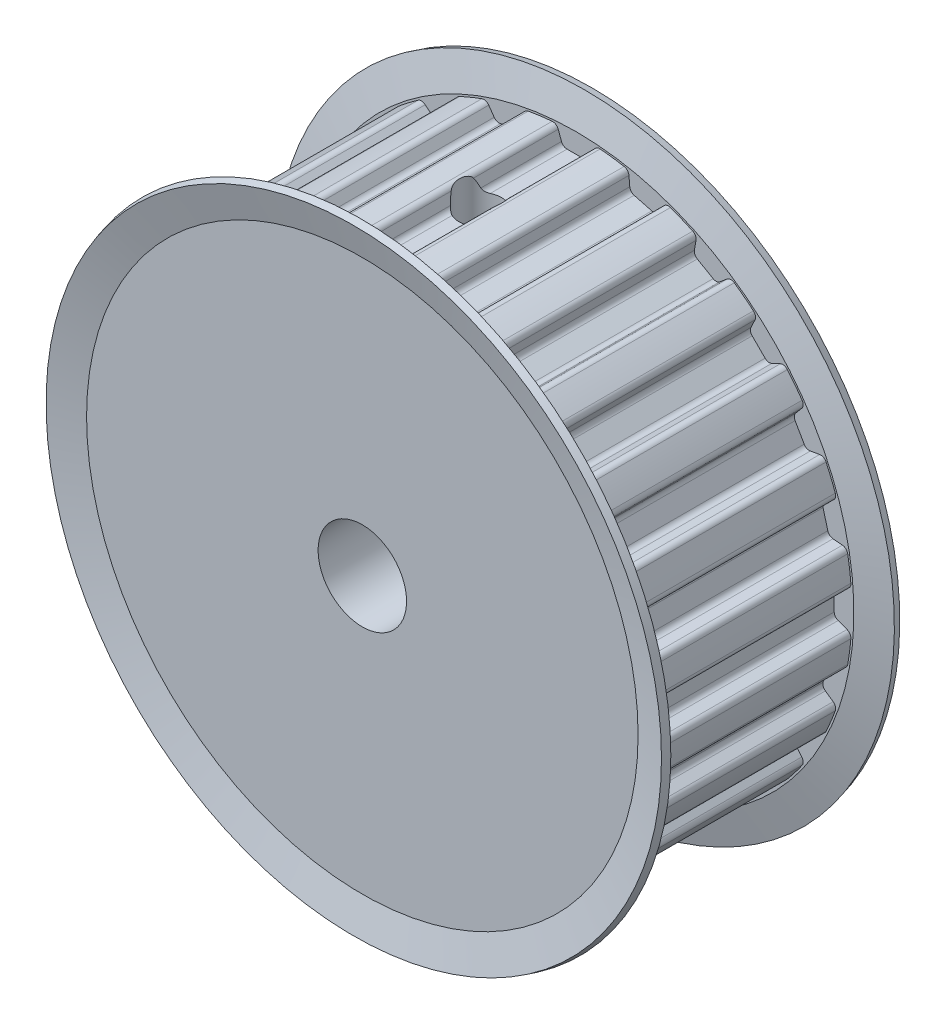
SolidWorks part; units mm, degrees
material "Д16Т ГОСТ 4784-74"
ref_plane "Front" through (0, 0, 0) normal (0, 0, 1) x (1, 0, 0)
ref_plane "Top" through (0, 0, 0) normal (0, 1, 0) x (1, 0, 0)
ref_plane "Right" through (0, 0, 0) normal (1, 0, 0) x (0, 0, -1)
sketch "support-front-body" plane through (0, 0, 0) normal (0, 0, 1) x (1, 0, 0)
  line L0 (0, 0) -> (0, 18.7) construction
  line L1 (0, 0) -> (0, -18.7) construction
  line L2 (0, 0) -> (18.7, 0) construction
  line L3 (0, 0) -> (-18.7, 0) construction
  circle A0 centre (0, 0) radius 18.7
  dimension "diam-outer" = 37.4
sketch "support-right-body" plane through (0, 0, 0) normal (1, 0, 0) x (0, 0, -1)
  line L0 (0, 0) -> (15, 0) construction
  line L1 (0, 18.7) -> (15, 18.7)
  line L2 (0, 18.7) -> (0, -18.7)
  line L3 (0, -18.7) -> (15, -18.7)
  line L4 (15, 18.7) -> (15, -18.7)
  dimension "width" = 15
sketch "support-right-hub" plane through (0, 0, 0) normal (1, 0, 0) x (0, 0, -1)
  line L0 (21, 0) -> (15, 0) construction
  line L1 (15, 13) -> (21, 13)
  line L2 (15, 13) -> (15, -13)
  line L3 (15, -13) -> (21, -13)
  line L4 (21, 13) -> (21, -13)
  line L5 (15, 18.7) -> (15, -18.7) construction
  line L6 (0, 0) -> (15, 0) construction
  line L8 (0, 18.7) -> (0, -18.7) construction
  dimension "diam-hub" = 26
  dimension "dist-hub" = 21
sketch "support-right-bore" plane through (0, 0, 0) normal (1, 0, 0) x (0, 0, -1)
  line L0 (0, 18.7) -> (0, -18.7) construction
  line L1 (0, 3) -> (21, 3)
  line L2 (0, 3) -> (0, -3)
  line L3 (0, -3) -> (21, -3)
  line L4 (21, 13) -> (21, -13) construction
  line L5 (21, 0) -> (0, 0) construction
  line L6 (0, 0) -> (15, 0) construction
  line L7 (21, 3) -> (21, -3)
  line L8 (21, -3) -> (21, 3) construction
  dimension "diam-bore" = 6
sketch "support-stop-screw-hole" plane through (0, 0, 0) normal (1, 0, 0) x (0, 0, -1)
  line L1 (6.5667, 50) -> (9.4333, 50)
  line L2 (6.5667, 50) -> (6.5667, -1)
  line L3 (8, -1) -> (9.4333, -1)
  line L4 (9.4333, 50) -> (9.4333, -1)
  line L5 (8, -1) -> (8, 50) construction
  line L6 (8, -1) -> (6.5667, -1)
  line L7 (0, 0) -> (8, 0) construction
  line L8 (0, 18.7) -> (0, -18.7) construction
  dimension "diam-stop-screw-hole" = 2.8665
  dimension "dist-stop-screw-hole" = 8
  dimension "depth-stop-screw-hole" = 51
  dimension "angle-stop-screw-hole" = 180
  dimension "height-stop-screw-hole" = 50
sketch "support-front-keygroove" plane through (0, 0, 0) normal (0, 0, 1) x (1, 0, 0)
  line L0 (0, 0) -> (0, -3) construction
  line L1 (-1, 5) -> (1, 5)
  line L2 (-1, 5) -> (-1, 2.8)
  line L3 (-1, 2.8) -> (1, 2.8)
  line L4 (1, 5) -> (1, 2.8)
  line L5 (0, 0) -> (0, 3) construction
  circle A0 centre (0, 0) radius 3 construction
  dimension "width-keygroove" = 2
  dimension "dist-keygroove" = 8
  dimension "height-keygroove" = 2.2
sketch "support-front-tooth" plane through (0, 0, 0) normal (0, 0, 1) x (1, 0, 0)
  line L0 (0, 0) -> (0, 19.8291) construction
  line L1 (-1.2157, 18.3675) -> (-0.9958, 17.7632)
  line L2 (-1.6264, 19.8291) -> (1.6264, 19.8291)
  line L3 (1.6264, 19.8291) -> (1.6264, 18.6291)
  line L4 (-1.6264, 19.8291) -> (-1.6264, 18.6291)
  line L5 (-2.5, 19.8291) -> (2.5, 19.8291) construction
  line L6 (1.6264, 18.6291) -> (2.5, 19.8291) construction
  line L7 (0, 18.7) -> (0, 17.5) construction
  line L8 (0, 18.7) -> (1.6264, 18.7) construction
  line L10 (-0.6199, 17.5) -> (0.6199, 17.5)
  line L11 (1.2157, 18.3675) -> (0.9958, 17.7632)
  line L12 (-0.9958, 17.7632) -> (-0.9, 17.5) construction
  line L13 (-0.9, 17.5) -> (-0.6199, 17.5) construction
  line L14 (0.9958, 17.7632) -> (0.9, 17.5) construction
  line L15 (0.9, 17.5) -> (0.6199, 17.5) construction
  circle A0 centre (0, 0) radius 18.7 construction
  arc A1 (-0.9958, 17.7632) -> (-0.6199, 17.5) centre (-0.6199, 17.9) ccw
  arc A3 (1.6264, 18.6291) -> (1.2157, 18.3675) centre (1.5916, 18.2307) ccw
  circle A4 centre (0, 0) radius 18.7 construction
  arc A5 (-1.6264, 18.6291) -> (-1.2157, 18.3675) centre (-1.5916, 18.2307) cw
  arc A6 (0.9958, 17.7632) -> (0.6199, 17.5) centre (0.6199, 17.9) cw
  point P26 (0, 17.5)
  dimension "rad-top" = 0.4
  dimension "rad-bottom" = 0.4
  dimension "height-tooth" = 1.2
  dimension "pitch" = 5
  dimension "angle" = 40
  dimension "width-tooth-bottom" = 1.8
sketch "support-right-flange" plane through (0, 0, 0) normal (1, 0, 0) x (0, 0, -1)
  line L0 (0, 16.625) -> (0, 18.7)
  line L1 (15, 18.7) -> (15, -18.7) construction
  line L2 (0, 18.7) -> (0.5, 18.7) construction
  line L3 (0.5, 18.834) -> (-0.0804, 21)
  line L4 (-0.5804, 20.866) -> (-0.0804, 21)
  line L5 (0.5, 18.834) -> (0.5, 16.625)
  line L6 (0.5, 16.625) -> (0, 16.625)
  line L7 (7.5, 18.7) -> (7.5, 0) construction
  line L8 (0, 18.7) -> (15, 18.7) construction
  line L9 (0, 18.7) -> (-0.5804, 20.866)
  line L10 (14.5, 16.625) -> (15, 16.625)
  line L11 (14.5, 18.834) -> (14.5, 16.625)
  line L12 (15.5804, 20.866) -> (15.0804, 21)
  line L13 (14.5, 18.834) -> (15.0804, 21)
  line L14 (15, 18.7) -> (15.5804, 20.866)
  line L15 (15, 16.625) -> (15, 18.7)
  line L16 (15, 0) -> (0, 0) construction
  line L17 (15, -16.625) -> (15, -18.7)
  line L18 (15, -18.7) -> (15.5804, -20.866)
  line L19 (14.5, -18.834) -> (15.0804, -21)
  line L20 (15.5804, -20.866) -> (15.0804, -21)
  line L21 (14.5, -18.834) -> (14.5, -16.625)
  line L22 (14.5, -16.625) -> (15, -16.625)
  line L23 (0.5, -16.625) -> (0, -16.625)
  line L24 (0.5, -18.834) -> (0.5, -16.625)
  line L25 (-0.5804, -20.866) -> (-0.0804, -21)
  line L26 (0.5, -18.834) -> (-0.0804, -21)
  line L27 (0, -18.7) -> (-0.5804, -20.866)
  line L28 (0, -16.625) -> (0, -18.7)
  line L29 (0, 0) -> (15, 0) construction
  line L30 (0, 18.7) -> (0.5, 18.834) construction
  line L31 (0.25, 16.625) -> (0.25, 17.6625) construction
  line L32 (0.25, 17.6625) -> (0.25, 18.7) construction
  line L33 (-0.3304, 20.933) -> (0.25, 18.767) construction
  line L34 (0, 18.7) -> (15, 18.7) construction
  line L35 (0, 18.7) -> (0, -18.7) construction
  dimension "angle-flange" = 15
  dimension "thickness-flange" = 0.5
  dimension "diam-flange-inner" = 33.25
  dimension "diam-flange-outer" = 42
  dimension "diam-flange-angle" = 37.4
ref_axis "ref-axis-center" through (0, 0, -15) along (0, 0, 1)
ref_plane "ref-plane-front" through (0, 0, 0) normal (0, 0, 1) x (1, 0, 0)
ref_plane "ref-plane-back" through (0, 0, -15) normal (0, 0, 1) x (1, 0, 0)
ref_plane "ref-plane-hub-front" through (0, 0, -15) normal (0, 0, 1) x (1, 0, 0)
ref_plane "ref-plane-hub-back" through (0, 0, -21) normal (0, 0, 1) x (1, 0, 0)
ref_plane "ref-plane-bore-front" through (0, 0, 0) normal (0, 0, 1) x (1, 0, 0)
ref_plane "ref-plane-bore-back" through (0, 0, -21) normal (0, 0, 1) x (1, 0, 0)
ref_plane "ref-plane-stop-screw-hole-top" through (0, 50, 0) normal (0, 1, 0) x (-1, 0, 0)
ref_axis "ref-axis-stop-screw-hole" through (0, 50, -8) along (0, -1, 0)
sketch "Sketch5" plane through (0, 0, 0) normal (1, 0, 0) x (0, 0, -1)
  line L0 (15, 18.7) -> (15, -18.7) construction
  line L1 (0, 18.7) -> (15, 18.7) construction
  line L2 (0, 18.7) -> (0, -18.7) construction
  line L3 (0, 0) -> (15, 0) construction
  line L4 (15, 18.7) -> (15, 0)
  line L5 (0, 18.7) -> (15, 18.7)
  line L6 (0, 18.7) -> (0, 0)
  line L7 (0, 0) -> (15, 0) construction
  line L8 (0, 0) -> (15, 0)
revolve "body" add sketch "Sketch5" angle 360 about L7
sketch "Sketch16" plane through (0, 0, 0) normal (1, 0, 0) x (0, 0, -1)
  line L0 (21, 13) -> (21, -13) construction
  line L1 (15, 13) -> (21, 13) construction
  line L2 (21, 0) -> (15, 0) construction
  line L3 (15, 13) -> (15, -13) construction
  line L4 (21, 13) -> (21, 0)
  line L5 (15, 13) -> (21, 13)
  line L6 (21, 0) -> (15, 0) construction
  line L7 (15, 13) -> (15, 0)
  line L8 (21, 0) -> (15, 0)
revolve "body-hub" add sketch "Sketch16" angle 360 about L6
sketch "Sketch17" plane through (0, 0, 0) normal (1, 0, 0) x (0, 0, -1)
  line L1 (21, 0) -> (0, 0) construction
  line L2 (0, 3) -> (21, 3) construction
  line L3 (0, 3) -> (0, -3) construction
  line L4 (21, 3) -> (21, -3) construction
  line L5 (21, 0) -> (0, 0) construction
  line L6 (0, 3) -> (21, 3)
  line L7 (0, 3) -> (0, 0)
  line L8 (21, 0) -> (0, 0)
  line L9 (21, 3) -> (21, 0)
revolve "body-bore" cut sketch "Sketch17" angle 360 about L5
sketch "Sketch19" plane through (0, 0, 0) normal (1, 0, 0) x (0, 0, -1)
  line L0 (6.5667, 50) -> (9.4333, 50) construction
  line L1 (8, -1) -> (8, 50) construction
  line L2 (9.4333, 50) -> (9.4333, -1) construction
  line L3 (8, -1) -> (9.4333, -1) construction
  line L4 (8, 50) -> (9.4333, 50)
  line L5 (8, -1) -> (8, 50) construction
  line L6 (9.4333, 50) -> (9.4333, -1)
  line L7 (8, -1) -> (9.4333, -1)
  line L8 (8, -1) -> (8, 50)
revolve "body-stop-screw-hole" cut sketch "Sketch19" angle 360 about L5
pattern_circular "pattern-stop-screw-hole" [suppressed] count 2 every 90 about axis through (0, 0, -15) along (0, 0, 1)
sketch "Sketch21" plane through (0, 0, 0) normal (0, 0, 1) x (1, 0, 0)
  line L0 (-1, 5) -> (1, 5) construction
  line L1 (-1, 5) -> (-1, 2.8) construction
  line L2 (-1, 2.8) -> (1, 2.8) construction
  line L3 (1, 5) -> (1, 2.8) construction
  line L4 (-1, 5) -> (1, 5)
  line L5 (-1, 5) -> (-1, 2.8)
  line L6 (-1, 2.8) -> (1, 2.8)
  line L7 (1, 5) -> (1, 2.8)
extrude "cut-keygroove" [suppressed] cut sketch "Sketch21" against normal up to surface (17.5 mm away)
sketch "Sketch23" plane through (0, 0, 0) normal (0, 0, 1) x (1, 0, 0)
  line L6 (1.6264, 19.8291) -> (-1.6264, 19.8291)
  line L7 (1.6264, 18.6291) -> (1.6264, 19.8291)
  line L8 (0.9958, 17.7632) -> (1.2157, 18.3675)
  line L9 (-0.6199, 17.5) -> (0.6199, 17.5)
  line L10 (-1.2157, 18.3675) -> (-0.9958, 17.7632)
  line L11 (-1.6264, 19.8291) -> (-1.6264, 18.6291)
  line L12 (1.6264, 19.8291) -> (-1.6264, 19.8291)
  line L13 (1.6264, 18.6291) -> (1.6264, 19.8291)
  line L14 (0.9958, 17.7632) -> (1.2157, 18.3675)
  line L15 (-0.6199, 17.5) -> (0.6199, 17.5)
  line L16 (-1.2157, 18.3675) -> (-0.9958, 17.7632)
  line L17 (-1.6264, 19.8291) -> (-1.6264, 18.6291)
  arc A4 (1.6264, 18.6291) -> (1.2157, 18.3675) centre (1.5916, 18.2307) ccw
  arc A5 (0.6199, 17.5) -> (0.9958, 17.7632) centre (0.6199, 17.9) ccw
  arc A6 (-0.9958, 17.7632) -> (-0.6199, 17.5) centre (-0.6199, 17.9) ccw
  arc A7 (-1.2157, 18.3675) -> (-1.6264, 18.6291) centre (-1.5916, 18.2307) ccw
  arc A8 (1.6264, 18.6291) -> (1.2157, 18.3675) centre (1.5916, 18.2307) ccw
  arc A9 (0.6199, 17.5) -> (0.9958, 17.7632) centre (0.6199, 17.9) ccw
  arc A10 (-0.9958, 17.7632) -> (-0.6199, 17.5) centre (-0.6199, 17.9) ccw
  arc A11 (-1.2157, 18.3675) -> (-1.6264, 18.6291) centre (-1.5916, 18.2307) ccw
  dimension "D1" = 0
extrude "cut-tooth" cut sketch "Sketch23" against normal up to surface (15 mm away) up to plane "ref-plane-back"
pattern_circular "pattern-tooth" count 24 over 360 about axis through (0, 0, -15) along (0, 0, 1) of "cut-tooth"
sketch "Sketch25" plane through (0, 0, 0) normal (1, 0, 0) x (0, 0, -1)
  line L0 (0, 0) -> (15, 0) construction
  line L1 (0.5, 16.625) -> (0, 16.625) construction
  line L2 (0.5, 18.834) -> (0.5, 16.625) construction
  line L4 (-0.5804, 20.866) -> (-0.0804, 21) construction
  line L5 (0, 18.7) -> (-0.5804, 20.866) construction
  line L6 (0, 16.625) -> (0, 18.7) construction
  line L7 (0, 0) -> (15, 0) construction
  line L8 (0.5, 16.625) -> (0, 16.625)
  line L9 (0.5, 18.834) -> (0.5, 16.625)
  line L10 (-0.5804, 20.866) -> (-0.0804, 21)
  line L11 (0.5, 18.834) -> (-0.0804, 21) construction
  line L12 (0, 18.7) -> (-0.5804, 20.866)
  line L13 (0, 16.625) -> (0, 18.7)
  line L14 (0.5, 18.834) -> (-0.0804, 21)
revolve "body-flange-front" add sketch "Sketch25" angle 360 about L7
sketch "Sketch26" plane through (0, 0, 0) normal (1, 0, 0) x (0, 0, -1)
  line L0 (15, 0) -> (0, 0) construction
  line L1 (14.5, 16.625) -> (15, 16.625) construction
  line L2 (14.5, 18.834) -> (14.5, 16.625) construction
  line L4 (15.5804, 20.866) -> (15.0804, 21) construction
  line L5 (15, 18.7) -> (15.5804, 20.866) construction
  line L6 (15, 16.625) -> (15, 18.7) construction
  line L7 (15, 0) -> (0, 0) construction
  line L8 (14.5, 16.625) -> (15, 16.625)
  line L9 (14.5, 18.834) -> (14.5, 16.625)
  line L10 (15.5804, 20.866) -> (15.0804, 21)
  line L11 (14.5, 18.834) -> (15.0804, 21) construction
  line L12 (15, 18.7) -> (15.5804, 20.866)
  line L13 (15, 16.625) -> (15, 18.7)
  line L14 (14.5, 18.834) -> (15.0804, 21)
revolve "body-flange-back" add sketch "Sketch26" angle 360 about L7
equation "\"diam-flange-angle@support-right-flange\" = \"diam-outer@support-front-body\""
equation "\"diam-flange-inner@support-right-flange\"=(\"diam-outer@support-front-body\" - 2 * \"height-tooth@support-front-tooth\" )  * 0.95"
